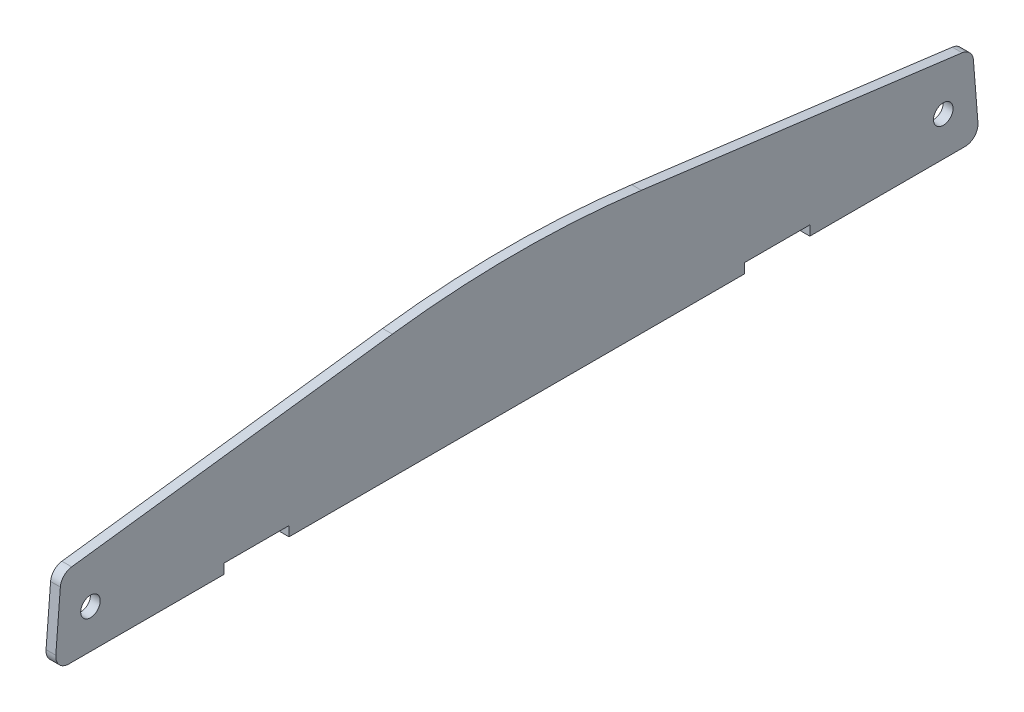
SolidWorks part; units mm, degrees
material "1023 Arkusz stali węglowej (SS)"
ref_plane "Płaszczyzna przednia" through (0, 0, 0) normal (0, 0, 1) x (1, 0, 0)
ref_plane "Płaszczyzna górna" through (0, 0, 0) normal (0, 1, 0) x (1, 0, 0)
ref_plane "Płaszczyzna prawa" through (0, 0, 0) normal (1, 0, 0) x (0, 0, -1)
sketch "Szkic1" plane through (0, 0, 0) normal (1, 0, 0) x (0, 0, -1)
  line L102 (-141.7303, -242.4083) -> (-140.3346, -224.9619)
  line L103 (-70.0759, -243.7273) -> (-70.0759, -246.7273)
  line L104 (-90.0759, -243.7273) -> (-70.0759, -243.7273)
  line L105 (-136.8574, -221.3135) -> (-38.3324, -208.646)
  line L106 (-70.0759, -246.7273) -> (-0.0759, -246.7273)
  line L107 (-90.0759, -246.7273) -> (-90.0759, -243.7273)
  line L108 (-137.7431, -246.7273) -> (-90.0759, -246.7273)
  line L109 (89.9241, -243.7273) -> (69.9241, -243.7273)
  line L110 (69.9241, -246.7273) -> (-0.0759, -246.7273)
  line L111 (89.9241, -246.7273) -> (89.9241, -243.7273)
  line L112 (137.5914, -246.7273) -> (89.9241, -246.7273)
  line L113 (141.5786, -242.4083) -> (140.1829, -224.9619)
  line L114 (136.7057, -221.3135) -> (38.1807, -208.646)
  line L115 (69.9241, -243.7273) -> (69.9241, -246.7273)
  circle A50 centre (-131.0759, -234.7273) radius 3
  circle A51 centre (130.9241, -234.7273) radius 3
  arc A52 (38.1807, -208.646) -> (-38.3324, -208.646) centre (-0.0759, -506.1967) ccw
  arc A53 (140.1829, -224.9619) -> (136.7057, -221.3135) centre (136.1957, -225.2808) ccw
  arc A54 (-136.8574, -221.3135) -> (-140.3346, -224.9619) centre (-136.3474, -225.2808) ccw
  arc A55 (137.5914, -246.7273) -> (141.5786, -242.4083) centre (137.5914, -242.7273) ccw
  arc A56 (-141.7303, -242.4083) -> (-137.7431, -246.7273) centre (-137.7431, -242.7273) ccw
extrude "Dodanie-wyciągnięcie1" add sketch "Szkic1" along normal blind 3
